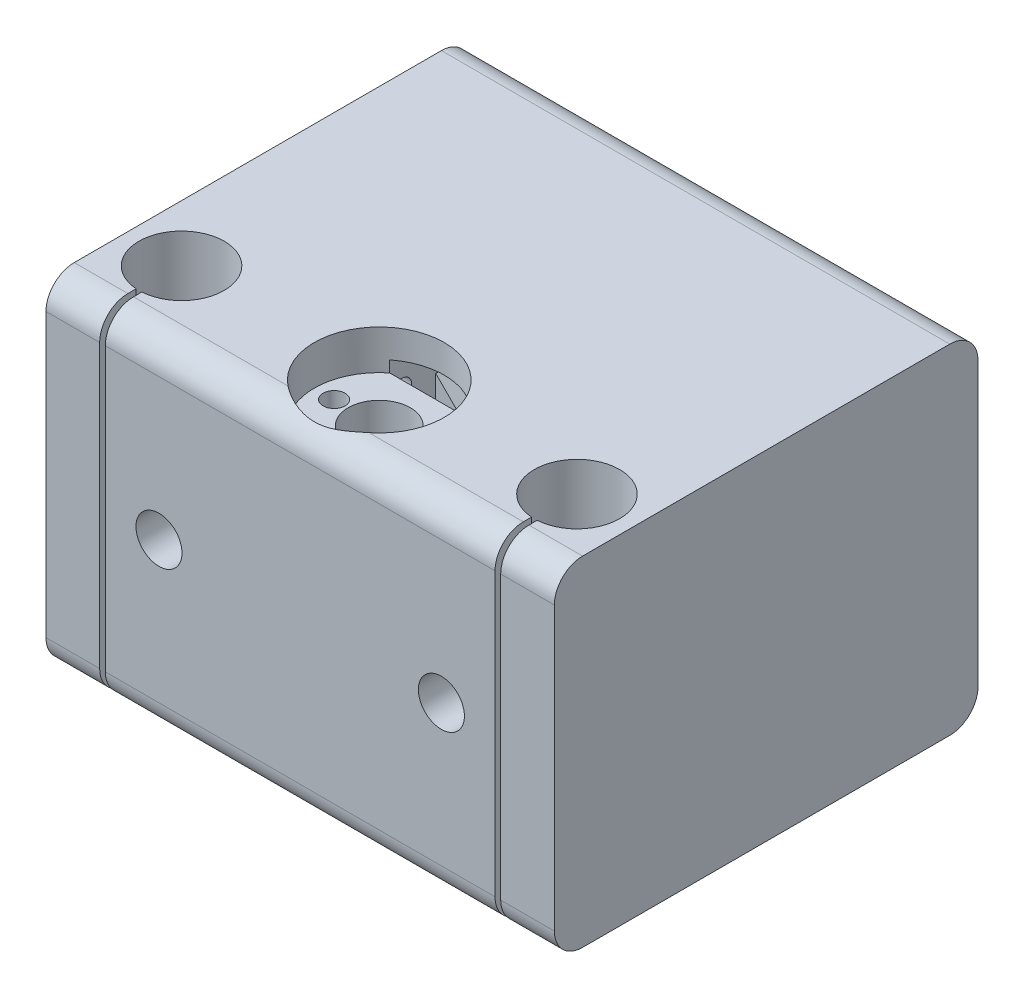
SolidWorks part; units mm, degrees
ref_plane "Front Plane" through (0, 0, 0) normal (0, 0, 1) x (1, 0, 0)
ref_plane "Top Plane" through (0, 0, 0) normal (0, 1, 0) x (1, 0, 0)
ref_plane "Right Plane" through (0, 0, 0) normal (1, 0, 0) x (0, 0, -1)
sketch "Sketch1" plane through (0, 0, 0) normal (1, 0, 0) x (0, 0, -1)
  line L1 (-27.5, -30) -> (27.5, -30)
  line L2 (-32.5, -25) -> (-32.5, 25)
  line L3 (-27.5, 30) -> (27.5, 30)
  line L4 (32.5, -25) -> (32.5, 25)
  line L5 (-32.5, -30) -> (32.5, 30) construction
  line L6 (-32.5, 30) -> (32.5, -30) construction
  arc A0 (-27.5, -30) -> (-32.5, -25) centre (-27.5, -25) cw
  arc A1 (27.5, -30) -> (32.5, -25) centre (27.5, -25) ccw
  arc A2 (27.5, 30) -> (32.5, 25) centre (27.5, 25) cw
  arc A3 (-32.5, 25) -> (-27.5, 30) centre (-27.5, 25) cw
  point P0 (0, 0)
  dimension "D3" = 5
  dimension "D1" = 60
  dimension "D2" = 65
extrude "Boss-Extrude1" add sketch "Sketch1" along normal blind 90
sketch "Sketch2" plane through (0, 30, 0) normal (0, 1, 0) x (1, 0, 0)
  line L0 (0, -18.5) -> (90, -18.5) construction
  line L1 (0, 27.5) -> (0, -27.5) construction
  line L2 (90, 27.5) -> (90, -27.5) construction
  line L3 (90, -32.5) -> (0, -32.5) construction
  circle A0 centre (10, -18.5) radius 7.55
  circle A1 centre (80, -18.5) radius 7.55
  circle A2 centre (45, -18.5) radius 5.5
  point P12 (45, -18.5)
  dimension "D1" = 15.1
  dimension "D2" = 70
  dimension "D5" = 11
  dimension "D3" = 35
  dimension "D4" = 14
extrude "Cut-Extrude1" cut sketch "Sketch2" against normal blind 90
sketch "Sketch3" plane through (0, 0, 32.5) normal (0, 0, 1) x (1, 0, 0)
  line L0 (0, 0) -> (90, 0) construction
  line L1 (0, 25) -> (0, -25) construction
  line L2 (90, 25) -> (90, -25) construction
  circle A0 centre (20, 0) radius 4.075
  circle A1 centre (70, 0) radius 4.075
  point P10 (45, 0)
  dimension "D2" = 8.15
  dimension "D3" = 8.15
  dimension "D1" = 50
  dimension "D4" = 25
extrude "Cut-Extrude2" cut sketch "Sketch3" against normal blind 90
sketch "Sketch4" plane through (0, 0, -32.5) normal (0, 0, -1) x (-1, 0, 0)
  line L0 (-87, 25) -> (-87, -25)
  line L1 (-3, -25) -> (-3, 25)
  line L2 (-3, -25) -> (-3, -35.9253)
  line L3 (-3, -35.9253) -> (-87, -35.9253)
  line L4 (0, -25) -> (0, 25)
  line L5 (0, 25) -> (-90, 25)
  line L6 (-90, 25) -> (-90, -25)
  line L7 (-3, 25) -> (-87, 25)
  line L9 (-90, -25) -> (0, -25)
  line L12 (-87, -35.9253) -> (-87, -25)
  circle M5 centre (-70, 0) radius 4.075
  circle M6 centre (-20, 0) radius 4.075
  line M8 (0, 25) -> (-90, 25)
  line M10 (-90, -25) -> (0, -25)
  dimension "D1" = 0
extrude "Cut-Extrude3" cut sketch "Sketch4" against normal blind 42 contours L1 L0 M10 M8 M6 M5 region at (45, 0, -32.5)
sketch "Sketch5" plane through (3, 0, 0) normal (1, 0, 0) x (0, 0, -1)
  line L0 (-9.5, 0) -> (12, 0) construction
  line L1 (12, 0) -> (12, 15.5) construction
  line L2 (12, 15.5) -> (-3.5, 15.5) construction
  line L3 (-9.5, -25) -> (-9.5, 25) construction
  circle A0 centre (12, 0) radius 11.5
  circle A1 centre (-3.5, 15.5) radius 1.75
  circle A2 centre (27.5, 15.5) radius 1.75
  circle A3 centre (27.5, -15.5) radius 1.75
  circle A4 centre (-3.5, -15.5) radius 1.75
  dimension "D2" = 23
  dimension "D4" = 3.5
  dimension "D1" = 21.5
  dimension "D3" = 15.5
  dimension "D5" = 2
  dimension "D6" = 2
extrude "Cut-Extrude4" cut sketch "Sketch5" against normal blind 42
ref_plane "Plane1" through (0, 0, 7.5) normal (0, 0, -1) x (-1, 0, 0)
sketch "Sketch10" plane through (0, 30, 0) normal (0, 1, 0) x (1, 0, 0)
  line L0 (10, -18.5) -> (10, -42.3505)
  line L1 (80, -18.5) -> (80, -42.3505)
extrude "Cut-Extrude-Thin1" cut sketch "Sketch10" against normal blind 70 thin thin type mid plane wall 1
chamfer "Chamfer2" distance 2 angle 45 1 edges at (3, 0, -23.5)
sketch "Sketch14" plane through (0, 0, 0) normal (-1, 0, 0) x (0, 0, 1)
  line L0 (-27.5, -30) -> (-42.5, -30)
  line L1 (-42.5, -30) -> (-42.5, 30)
  line L2 (-42.5, 30) -> (-27.5, 30)
  line L3 (-32.5, 25) -> (-32.5, -25)
  arc A0 (-27.5, 30) -> (-32.5, 25) centre (-27.5, 25) ccw
  arc A1 (-32.5, -25) -> (-27.5, -30) centre (-27.5, -25) ccw
  dimension "D1" = 10
extrude "Boss-Extrude4" add sketch "Sketch14" against normal up to surface (3 mm away) up to face at (3, 0, 1.5)
sketch "Sketch15" plane through (90, 0, 0) normal (1, 0, 0) x (0, 0, -1)
  line L0 (27.5, -30) -> (42.5, -30)
  line L1 (42.5, -30) -> (42.5, 30)
  line L2 (42.5, 30) -> (27.5, 30)
  line L3 (27.5, 30) -> (27.5, -30)
  line L4 (42.5, -30) -> (42.5, 30) construction
extrude "Boss-Extrude5" add sketch "Sketch15" against normal up to surface (3 mm away) up to face at (87, 0, -11.5)
fillet "Fillet1" radius 5 4 edges at (88.5, 30, -42.5) (1.5, 30, -42.5) (1.5, -30, -42.5) (88.5, -30, -42.5)
sketch "Sketch16" plane through (0, -25, 0) normal (0, 1, 0) x (1, 0, 0)
  line L1 (3, -9.5) -> (87, -9.5)
  line L2 (3, -9.5) -> (3, 32.5)
  line L3 (3, 32.5) -> (87, 32.5)
  line L4 (87, -9.5) -> (87, 32.5)
extrude "Cut-Extrude5" cut sketch "Sketch16" against normal blind 10
sketch "Sketch17" plane through (3, 0, 0) normal (1, 0, 0) x (0, 0, -1)
  line L0 (32.5, 25) -> (42.5, 25)
  line L1 (37.5, 30) -> (27.5, 30)
  arc A0 (42.5, 25) -> (37.5, 30) centre (37.5, 25) ccw
  arc A1 (27.5, 30) -> (32.5, 25) centre (27.5, 25) cw
extrude "Boss-Extrude6" add sketch "Sketch17" along normal up to surface (84 mm away) up to face at (87, 6.3794, -25.5133)
sketch "Sketch18" plane through (0, 0, -42.5) normal (0, 0, -1) x (-1, 0, 0)
  line L0 (-61, 0) -> (-61, 25)
  line L1 (-87, 25) -> (-3, 25) construction
  line L2 (-61, 25) -> (-87, 25)
  line L3 (-87, 25) -> (-87, -9)
  line L4 (-87, 25) -> (-87, -25) construction
  line L5 (-87, -9) -> (-70, -9)
  circle A0 centre (-70, 0) radius 4.075
  arc A1 (-70, -9) -> (-61, 0) centre (-70, 0) ccw
  dimension "D1" = 8.15
  dimension "D2" = 18
extrude "Boss-Extrude7" add sketch "Sketch18" against normal blind 9
sketch "Sketch19" plane through (0, 0, -42.5) normal (0, 0, -1) x (-1, 0, 0)
  line L0 (-63.636, -6.364) -> (-67.1185, -2.8815)
  line L1 (-67.1185, -2.8815) -> (-68.7086, -1.2914)
  line L2 (-63.636, -6.364) -> (-62.3187, -7.6813)
  arc A0 (-70, -9) -> (-61, 0) centre (-70, 0) ccw construction
  circle A1 centre (-70, 0) radius 4.075 construction
extrude "Cut-Extrude-Thin3" cut sketch "Sketch19" against normal blind 9 and the other way through all thin thin type mid plane wall 1
sketch "Sketch21" plane through (0, 30, 0) normal (0, 1, 0) x (1, 0, 0)
  circle A0 centre (45, -18.5) radius 11.5
  dimension "D1" = 23
extrude "Cut-Extrude7" cut sketch "Sketch21" against normal blind 7
sketch "Sketch22" plane through (0, 23, 0) normal (0, 1, 0) x (1, 0, 0)
  line L0 (45, -18.5) -> (53, -18.5) construction
  line L1 (45, -18.5) -> (53, -18.5) construction
  line L2 (45, -18.5) -> (45, -26.5) construction
  circle A0 centre (53, -18.5) radius 1.95
  circle A1 centre (45, -26.5) radius 1.95
  circle A2 centre (37, -18.5) radius 1.95
  dimension "D1" = 3.9
  dimension "D2" = 8
  dimension "D4" = 90
  dimension "D3" = 3
extrude "Cut-Extrude8" cut sketch "Sketch22" against normal blind 20
sketch "Sketch23" plane through (3, 0, 0) normal (1, 0, 0) x (0, 0, -1)
  line L0 (-9.5, 25) -> (42.5, 25) construction
  line L1 (4.5, 25) -> (19.5, 25)
  line L2 (4.5, 25) -> (4.5, 20)
  line L3 (4.5, 20) -> (19.5, 20)
  line L4 (19.5, 25) -> (19.5, 20)
  line L5 (27.5, 15.5) -> (19.5, 20) construction
  line L6 (4.5, 20) -> (-3.5, 15.5) construction
  point P7 (16.5, 25)
  dimension "D1" = 15
  dimension "D2" = 5
extrude "Cut-Extrude9" cut sketch "Sketch23" against normal blind 20
sketch "Sketch24" plane through (87, 0, 0) normal (-1, 0, 0) x (0, 0, 1)
  line L0 (-42.5, -21) -> (-33.5, -21)
  line L1 (-42.5, -9) -> (-42.5, -25) construction
  line L2 (-33.5, -21) -> (-33.5, -30)
  line L3 (-37.5, -30) -> (9.5, -30) construction
  line L4 (-33.5, -30) -> (-37.5, -30)
  line L5 (-42.5, -25) -> (-42.5, -21)
  arc A0 (-37.5, -30) -> (-42.5, -25) centre (-37.5, -25) cw
  dimension "D1" = 9
  dimension "D2" = 9
extrude "Boss-Extrude8" add sketch "Sketch24" along normal up to next
chamfer "Chamfer3" distance 5 angle 45 3 edges at (87, -21, -38) (3, -21, -38) (87, -9, -38)
chamfer "Chamfer4" distance 5 angle 45 1 edges at (61, 25, -38)
